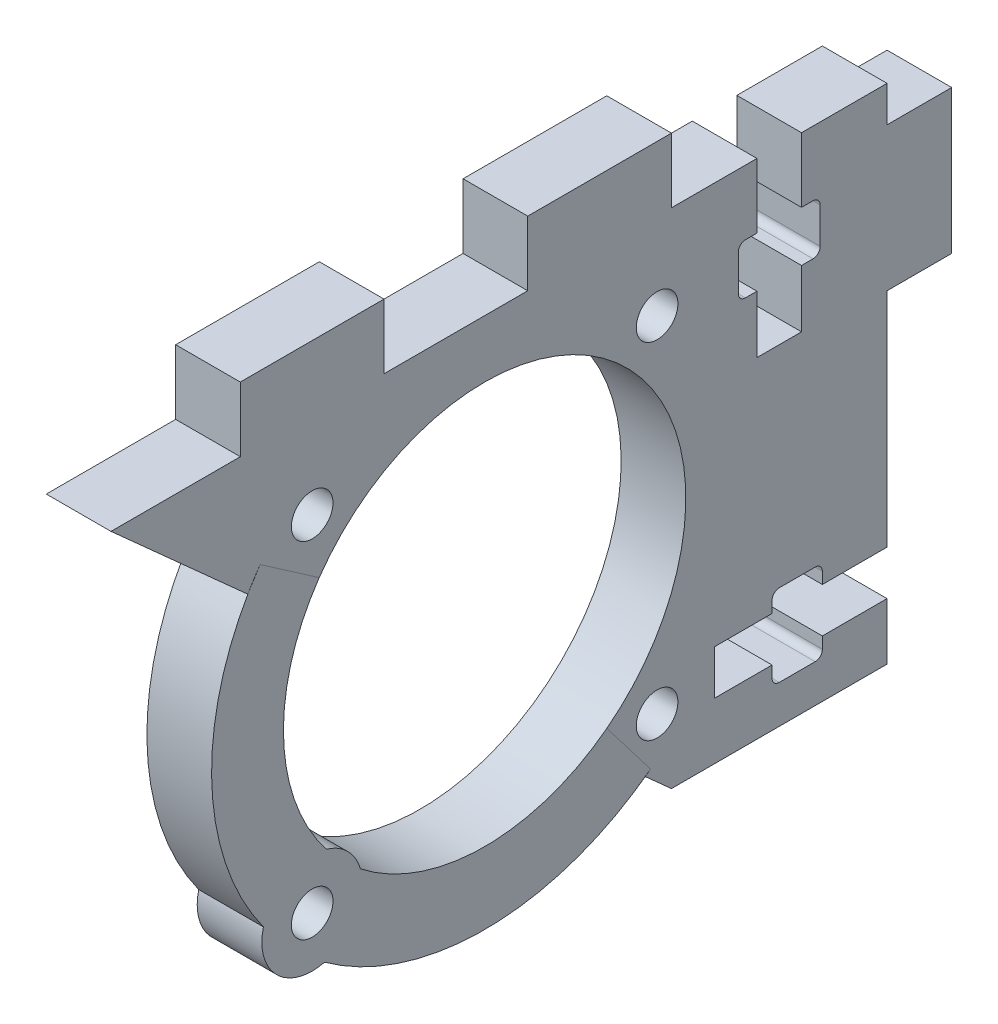
SolidWorks part; units mm, degrees
ref_plane "Front Plane" through (0, 0, 0) normal (0, 0, 1) x (1, 0, 0)
ref_plane "Top Plane" through (0, 0, 0) normal (0, 1, 0) x (1, 0, 0)
ref_plane "Right Plane" through (0, 0, 0) normal (1, 0, 0) x (0, 0, -1)
sketch "Sketch1" plane through (0, 0, 0) normal (1, 0, 0) x (0, 0, -1)
  line L0 (0, 0) -> (0, -35)
  line L1 (0, -35) -> (-54, 0)
  line L2 (-54, 0) -> (0, 0)
  dimension "D1" = 35
  dimension "D2" = 54
extrude "Boss-Extrude1" add sketch "Sketch1" along normal blind 4.5
sketch "Sketch2" plane through (4.5, 0, 0) normal (1, 0, 0) x (0, 0, -1)
  line L0 (0, -35) -> (0, 0) construction
  line L1 (-4.5, -2.5) -> (4.5, -2.5)
  line L2 (-4.5, -2.5) -> (-4.5, -12.5)
  line L3 (-4.5, -12.5) -> (4.5, -12.5)
  line L4 (4.5, -2.5) -> (4.5, -12.5)
  line L5 (-4.5, -2.5) -> (4.5, -12.5) construction
  line L6 (-4.5, -12.5) -> (4.5, -2.5) construction
  line L7 (0, 0) -> (-54, 0) construction
  point P0 (0, -7.5)
  dimension "D1" = 10
  dimension "D2" = 7.5
  dimension "D3" = 4.5
extrude "Boss-Extrude2" add sketch "Sketch2" against normal through all
sketch "Sketch3" plane through (4.5, 0, 0) normal (1, 0, 0) x (0, 0, -1)
  line L0 (0, -35) -> (-15, -35)
  line L1 (0, -25) -> (-54, 0)
  line L4 (0, -35) -> (0, -12.5) construction
  line L5 (0, -25) -> (0, -35)
  line L6 (-54, 0) -> (-15, -35)
  dimension "D1" = 15
  dimension "D2" = 10
extrude "Boss-Extrude3" add sketch "Sketch3" against normal through all
sketch "Sketch4" plane through (4.5, 0, 0) normal (1, 0, 0) x (0, 0, -1)
  line L0 (0, -29.5) -> (-12, -29.5) construction
  line L1 (0, -35) -> (0, -12.5) construction
  line L2 (0, -27.95) -> (-12, -27.95) construction
  line L3 (-12, -27.95) -> (-12, -31.05) construction
  line L4 (0, -31.05) -> (0, -27.95)
  line L5 (0, -27.95) -> (-4.5, -27.95)
  line L6 (-4.5, -27.95) -> (-4.5, -27.15)
  line L7 (-5, -26.65) -> (-7.5, -26.65)
  line L8 (-8, -27.15) -> (-8, -27.95)
  line L9 (-8, -27.95) -> (-12, -27.95)
  line L10 (-12, -27.95) -> (-12, -31.05)
  line L12 (0, -31.05) -> (-12, -31.05) construction
  line L13 (-8, -31.05) -> (-12, -31.05)
  line L14 (-8, -31.85) -> (-8, -31.05)
  line L15 (-5, -32.35) -> (-7.5, -32.35)
  line L16 (-4.5, -31.05) -> (-4.5, -31.85)
  line L17 (0, -31.05) -> (-4.5, -31.05)
  line L18 (4.5, -12.5) -> (4.5, -2.5) construction
  line L19 (0, -18.5) -> (-33.3857, -18.5) construction
  line L20 (-54, 0) -> (-15, -35) construction
  line L37 (0, -31.05) -> (-12, -31.05) construction
  arc A0 (-8, -31.85) -> (-7.5, -32.35) centre (-7.5, -31.85) ccw
  arc A1 (-5, -32.35) -> (-4.5, -31.85) centre (-5, -31.85) ccw
  arc A2 (-4.5, -27.15) -> (-5, -26.65) centre (-5, -27.15) ccw
  arc A3 (-7.5, -26.65) -> (-8, -27.15) centre (-7.5, -27.15) ccw
  point P10 (4.5, -7.5)
  point P20 (-8, -32.35)
  point P23 (-4.5, -32.35)
  point P26 (-4.5, -26.65)
  point P29 (-8, -26.65)
  dimension "D7" = 0.5
  dimension "D1" = 12
  dimension "D2" = 1.55
  dimension "D3" = 2.85
  dimension "D4" = 3.5
  dimension "D5" = 8
  dimension "D6" = 22
extrude "Cut-Extrude1" cut sketch "Sketch4" against normal through all
sketch "Sketch5" plane through (4.5, 0, 0) normal (1, 0, 0) x (0, 0, -1)
  line L0 (0, 0) -> (-54, 0) construction
  line L1 (-25, 4.5) -> (-15, 4.5)
  line L2 (-25, 4.5) -> (-25, 0)
  line L3 (0, 0) -> (-54, 0) construction
  line L4 (-15, 4.5) -> (-15, 0)
  line L5 (-25, 4.5) -> (-20, 0) construction
  line L6 (-20, 0) -> (-15, 4.5) construction
  line L7 (-30, 0) -> (-30, 4.5) construction
  line L8 (-40, 0) -> (-45, 4.5) construction
  line L9 (-35, 4.5) -> (-40, 0) construction
  line L10 (-45, 4.5) -> (-45, 0)
  line L12 (-35, 4.5) -> (-35, 0)
  line L13 (-35, 4.5) -> (-45, 4.5)
  line L14 (-20, 0) -> (-15, 4.5) construction
  line L15 (-15, 0) -> (-25, 0)
  line L16 (-35, 0) -> (-45, 0)
  point P0 (-20, 0)
  point P14 (-40, 0)
  dimension "D3" = 4.5
  dimension "D1" = 20
  dimension "D2" = 10
  dimension "D4" = 20
  dimension "D5" = 5
extrude "Boss-Extrude4" add sketch "Sketch5" against normal through all
sketch "Sketch8" [suppressed] plane through (4.5, 0, 0) normal (1, 0, 0) x (0, 0, -1)
  line L0 (-15, -30) -> (-27, -30) construction
  line L1 (-15, -35) -> (-27, -35)
  line L2 (-15, -25) -> (-27, -25)
  line L3 (-15, -35) -> (0, -35) construction
  line L4 (-15, -25) -> (-15, -35)
  arc A1 (-27, -25) -> (-27, -35) centre (-27, -30) ccw
  dimension "D5" = 5
  dimension "D1" = 0
  dimension "D2" = 12
  dimension "D3" = 0
  dimension "D4" = 10
extrude "Boss-Extrude5" [suppressed] add sketch "Sketch8" against normal up to surface (4.5 mm away) up to face at (0, -17.3125, 11.9375)
sketch "Sketch9" [suppressed] plane through (4.5, 0, 0) normal (1, 0, 0) x (0, 0, -1)
  line L0 (-27, -30) -> (-22, -30) construction
  line L1 (-27, -27) -> (-22, -27)
  line L2 (-27, -33) -> (-22, -33)
  arc A0 (-27, -27) -> (-27, -33) centre (-27, -30) ccw
  arc A1 (-22, -33) -> (-22, -27) centre (-22, -30) ccw
  point P3 (-24.5, -30)
  dimension "D1" = 3
  dimension "D2" = 5
extrude "Cut-Extrude3" [suppressed] cut sketch "Sketch9" against normal through all
sketch "Sketch10" plane through (0, 0, 0) normal (-1, 0, 0) x (0, 0, 1)
  line L0 (15, -35) -> (54, -12)
  line L1 (54, -12) -> (54, 0)
  line L3 (54, 0) -> (15, -35)
  dimension "D1" = 12
extrude "Boss-Extrude6" [suppressed] add sketch "Sketch10" against normal through all
sketch "Sketch6" plane through (4.5, 0, 0) normal (1, 0, 0) x (0, 0, -1)
  line L0 (-30, 0) -> (-30, -11) construction
  line L1 (-25, 0) -> (-35, 0) construction
  line L2 (-28.45, -11) -> (-31.55, -11) construction
  line L3 (-31.55, -11) -> (-31.55, 0) construction
  line L4 (-28.45, 0) -> (-31.55, 0)
  line L5 (-31.55, 0) -> (-31.55, -4.5)
  line L6 (-31.55, -4.5) -> (-32.35, -4.5)
  line L7 (-32.85, -5) -> (-32.85, -7.5)
  line L8 (-32.35, -8) -> (-31.55, -8)
  line L9 (-31.55, -8) -> (-31.55, -11)
  line L10 (-31.55, -11) -> (-28.45, -11)
  line L11 (-28.45, -11) -> (-28.45, 0) construction
  line L12 (-28.45, -8) -> (-28.45, -11)
  line L13 (-27.65, -8) -> (-28.45, -8)
  line L14 (-27.15, -5) -> (-27.15, -7.5)
  line L15 (-28.45, -4.5) -> (-27.65, -4.5)
  line L16 (-28.45, 0) -> (-28.45, -4.5)
  arc A0 (-32.85, -7.5) -> (-32.35, -8) centre (-32.35, -7.5) ccw
  arc A1 (-32.35, -4.5) -> (-32.85, -5) centre (-32.35, -5) ccw
  arc A2 (-27.65, -4.5) -> (-27.15, -5) centre (-27.65, -5) cw
  arc A3 (-27.15, -7.5) -> (-27.65, -8) centre (-27.65, -7.5) cw
  point P12 (-32.85, -8)
  point P15 (-32.85, -4.5)
  point P26 (-27.15, -4.5)
  point P27 (-27.15, -8)
  dimension "D2" = 1.55
  dimension "D4" = 3.5
  dimension "D6" = 0.5
  dimension "D1" = 11
  dimension "D3" = 8
  dimension "D5" = 2.85
extrude "Cut-Extrude2" [suppressed] cut sketch "Sketch6" against normal through all
sketch "Sketch11" plane through (0, 0, 0) normal (-1, 0, 0) x (0, 0, 1)
  line L0 (7.5, 0) -> (7.5, -12) construction
  line L1 (0, 0) -> (15, 0) construction
  line L2 (5.95, -12) -> (9.05, -12)
  line L3 (9.05, -12) -> (9.05, -8)
  line L4 (9.05, -8) -> (9.85, -8)
  line L5 (10.35, -7.5) -> (10.35, -5)
  line L6 (9.85, -4.5) -> (9.05, -4.5)
  line L7 (9.05, -4.5) -> (9.05, 0)
  line L8 (9.05, 0) -> (5.95, 0)
  line L9 (9.05, -8) -> (9.05, -4.5) construction
  line L10 (0, 0) -> (15, 0) construction
  line L11 (5.95, -8) -> (5.95, -4.5) construction
  line L12 (5.95, -4.5) -> (5.95, 0)
  line L13 (5.15, -4.5) -> (5.95, -4.5)
  line L14 (4.65, -7.5) -> (4.65, -5)
  line L15 (5.95, -8) -> (5.15, -8)
  line L16 (5.95, -12) -> (5.95, -8)
  arc A0 (10.35, -5) -> (9.85, -4.5) centre (9.85, -5) ccw
  arc A1 (5.15, -4.5) -> (4.65, -5) centre (5.15, -5) ccw
  arc A2 (9.85, -8) -> (10.35, -7.5) centre (9.85, -7.5) ccw
  arc A3 (4.65, -7.5) -> (5.15, -8) centre (5.15, -7.5) ccw
  point P11 (7.5, 0)
  point P22 (10.35, -4.5)
  point P25 (4.65, -4.5)
  point P28 (10.35, -8)
  point P31 (4.65, -8)
  dimension "D7" = 0.5
  dimension "D1" = 12
  dimension "D3" = 2.85
  dimension "D8" = 0.5
  dimension "D2" = 3.5
  dimension "D4" = 8
  dimension "D5" = 1.55
  dimension "D6" = 0
extrude "Cut-Extrude4" cut sketch "Sketch11" against normal through all
sketch "Sketch12" plane through (0, 0, 0) normal (-1, 0, 0) x (0, 0, 1)
  line L0 (28, -18) -> (16, -6) construction
  line L1 (28, -18) -> (28, -4) construction
  line L2 (28, -18) -> (40, -6) construction
  line L3 (28, -18) -> (14, -18) construction
  line L4 (28, -18) -> (16, -30) construction
  line L5 (28, -18) -> (16, -6) construction
  line L6 (0, -27.95) -> (0, -12.5) construction
  line L7 (25, 0) -> (35, 0) construction
  circle A0 centre (28, -18) radius 14
  circle A1 centre (16, -6) radius 1.45
  circle A2 centre (40, -6) radius 1.45
  circle A3 centre (16, -30) radius 1.45
  dimension "D1" = 28
  dimension "D2" = 2.9
  dimension "D3" = 12
  dimension "D4" = 45
  dimension "D5" = 28
  dimension "D6" = 18
extrude "FanCutout" cut sketch "Sketch12" against normal through all
sketch "Sketch13" plane through (0, 0, 0) normal (-1, 0, 0) x (0, 0, 1)
  line L0 (39.5107, -10.0311) -> (43.6217, -7.185)
  line L1 (19.4957, -29.121) -> (16.4584, -33.0928)
  line L6 (28, -18) -> (54, 0) construction
  line L7 (28, -18) -> (15, -35) construction
  arc A0 (19.4957, -29.121) -> (39.5107, -10.0311) centre (28, -18) ccw
  arc A1 (16.4584, -33.0928) -> (43.6217, -7.185) centre (28, -18) ccw
  arc A3 (40.643, -11.9871) -> (20.6593, -29.9212) centre (28, -18) ccw construction
  dimension "D1" = 5
extrude "Boss-Extrude7" add sketch "Sketch13" against normal through all
sketch "Sketch14" plane through (0, 0, 0) normal (-1, 0, 0) x (0, 0, 1)
  line L0 (28, -4) -> (28, -32) construction
  line L1 (28, -18) -> (40, -30) construction
  circle A0 centre (28, -18) radius 14 construction
  circle A1 centre (40, -30) radius 3.5
  dimension "D2" = 7
  dimension "D1" = 45
  dimension "D3" = 12
extrude "Boss-Extrude8" add sketch "Sketch14" against normal through all
sketch "Sketch15" plane through (0, 0, 0) normal (-1, 0, 0) x (0, 0, 1)
  line L0 (42.4749, -32.4749) -> (28, -18) construction
  arc A0 (39.1388, -33.3924) -> (43.3924, -29.1388) centre (40, -30) ccw construction
  circle A1 centre (40, -30) radius 1.45
  dimension "D1" = 2.9
extrude "Cut-Extrude6" cut sketch "Sketch15" against normal through all
sketch "Sketch16" [suppressed] plane through (4.5, 0, 0) normal (1, 0, 0) x (0, 0, -1)
  line L0 (0, -34.5) -> (-39, -34.5) construction
  line L1 (0, -27.95) -> (0, -12.5) construction
  line L2 (-15, -34.5) -> (-39, -34.5) construction
  line L3 (-15, -38.5) -> (-39, -38.5)
  line L4 (-15, -30.5) -> (-39, -30.5)
  arc A0 (-15, -38.5) -> (-15, -30.5) centre (-15, -34.5) ccw
  arc A1 (-39, -30.5) -> (-39, -38.5) centre (-39, -34.5) ccw
  point P5 (-27, -34.5)
  point P12 (0, -20.225)
  dimension "D1" = 4
  dimension "D2" = 34.5
  dimension "D3" = 39
  dimension "D4" = 15
extrude "Boss-Extrude9" [suppressed] add sketch "Sketch16" against normal through all
sketch "Sketch17" [suppressed] plane through (4.5, 0, 0) normal (1, 0, 0) x (0, 0, -1)
  line L0 (-43, -34.5) -> (0, -34.5) construction
  line L1 (0, -27.75) -> (0, -12.5) construction
  line L2 (-26.5, -34.5) -> (-26.5, -20.0064) construction
  arc A0 (-42.1823, -32.0766) -> (-39, -38.5) centre (-39, -34.5) ccw construction
  circle A1 centre (-39, -34.5) radius 1.55
  circle A2 centre (-14, -34.5) radius 1.55
  dimension "D1" = 2.9
  dimension "D2" = 12.5
extrude "Cut-Extrude7" [suppressed] cut sketch "Sketch17" against normal through all
sketch "Sketch18" [suppressed] plane through (4.5, 0, 0) normal (1, 0, 0) x (0, 0, -1)
  line L0 (-15, -38.5) -> (0, -35)
  line L1 (0, -35) -> (-11.0314, -35)
  line L2 (-11.0314, -35) -> (-15, -38.5)
extrude "Boss-Extrude10" [suppressed] add sketch "Sketch18" against normal through all
sketch "Sketch20" [suppressed] plane through (4.5, 0, 0) normal (1, 0, 0) x (0, 0, -1)
  line L0 (0, -35) -> (0, -31.05) construction
  line L1 (-9, -38) -> (-37.9081, -38)
  line L2 (-40.7232, -36.0371) -> (-54, 0)
  line L3 (-54, 0) -> (-15, -35)
  line L4 (-15, -35) -> (-6, -35)
  line L5 (-9, -38) -> (-6, -35)
  line L6 (-40.7232, -36.0371) -> (-40, -38) construction
  line L7 (-40, -38) -> (-37.9081, -38) construction
  arc A1 (-37.9081, -38) -> (-40.7232, -36.0371) centre (-37.9081, -35) cw
  point P0 (0, -33.025)
  point P14 (-40, -38)
  dimension "D3" = 6
  dimension "D4" = 3
  dimension "D1" = 40
  dimension "D2" = 3
  dimension "D5" = 135
extrude "Boss-Extrude11" [suppressed] add sketch "Sketch20" against normal through all
sketch "Sketch21" [suppressed] plane through (4.5, 0, 0) normal (1, 0, 0) x (0, 0, -1)
  line L0 (0, -34.5) -> (-41.2895, -34.5) construction
  line L1 (0, -35) -> (0, -31.05) construction
  line L2 (-54, 0) -> (-40.7232, -36.0371) construction
  line L3 (0, -27.95) -> (0, -12.5) construction
  circle A0 centre (-36, -34.5) radius 1.45
  circle A1 centre (-11, -34.5) radius 1.45
  dimension "D2" = 2.9
  dimension "D3" = 2.9
  dimension "D1" = 25
  dimension "D4" = 34.5
  dimension "D5" = 11
extrude "Cut-Extrude8" [suppressed] cut sketch "Sketch21" against normal through all
sketch "Sketch22" [suppressed] plane through (4.5, 0, 0) normal (1, 0, 0) x (0, 0, -1)
  line L0 (0, -27.95) -> (0, -12.5) construction
  line L1 (-25, 0) -> (-35, 0) construction
  circle A0 centre (-28, -18) radius 13.25
  dimension "D2" = 18
  dimension "D3" = 26.5
  dimension "D1" = 28
extrude "Cut-Extrude9" [suppressed] cut sketch "Sketch22" against normal through all
equation "\"X-ROD-SPACING\"=45"
equation "\"Y-ROD-SPACING\"=75"
equation "\"Z-ROD-SPACING\"=17.5"
equation "\"Y-BED-OFFSET\"=2"
equation "\"Y-BED-ROD-INSET\"=3.5"
equation "\"Y-BED-SCREW-SPACING\"=209"
equation "\"Y-BED-SCREW-CUTOUT-SLOT-HEIGHT\"=2"
equation "\"T-SLOT-NUT-FILLET-RADIUS\"=0.5"
equation "\"T-SLOT-SCREW-SHAFT-RADIUS\"=1.55"
equation "\"T-SLOT-SCREW-SHAFT-CUTOUT-LENGTH\"=11.0"
equation "\"T-SLOT-NUT-DEPTH\"=3.5"
equation "\"T-SLOT-NUT-WIDTH\"=2.85"
equation "\"T-SLOT-NUT-END-DISTANCE\"=8"
equation "\"ACRYLIC-THICKNESS\"=10"
equation "\"ACRYLIC-THICKNESS2\"=4.5"
equation "\"ACRYLIC-TAB-CUTOUT-SIZE\"=\"ACRYLIC-THICKNESS\"+\"ACRYLIC-TAB-TOLERANCE\"*2"
equation "\"ACRYLIC-TAB-WIDTH\"=\"ACRYLIC-THICKNESS\""
equation "\"ACRYLIC-M3-HOLE\"=2.9"
equation "\"SMOOTHROD-CAP-SCREW-DISTANCE\"=20"
equation "\"FRAME-WIDTH-INNER\"=370"
equation "\"NEMA17-HOLE-SPACING\"=31"
equation "\"NEMA17-CENTRAL-CUTOUT\"=22.5"
equation "\"Z-BRACKET-REACH\"=55"
equation "\"Z-ROD-INSET\"=16"
equation "\"TOP-BRACKET-SPACING\"=40"
equation "\"SMOOTHROD-X-LENGTH\"=350"
equation "\"SMOOTHROD-Y-LENGTH\"=350"
equation "\"SMOOTHROD-Z-LENGTH\"=350"
equation "\"SMOOTHROD-TIGHTENING-HEADROOM\"=.25"
equation "\"LEADSCREW-Z-LENGTH\"=300"
equation "\"SCREW-LENGTH-FRAME\"=\"ACRYLIC-THICKNESS\" + 10"
equation "\"SCREW-LENGTH-MOTOR\"=\"ACRYLIC-THICKNESS\" + 5"
equation "\"SCREW-LENGTH-EXTRUDER\"=28"
equation "\"SCREW-HEAD-RADIUS\"=6"
equation "\"PRINTED-X-SMOOTHROD-DIAMETER\"=9.0"
equation "\"PRINTED-X-SMOOTHROD-CUTOUT\"=10"
equation "\"PRINTED-X-BASE-HEIGHT\"=10"
equation "\"PRINTED-LM8UU-CUTOUT-SIZE\"=15.5"
equation "\"PRINTED-LM8UU-CUTOUT-LENGTH\"=24.5"
equation "\"PRINTED-X-IDLER-HEIGHT\"=16"
equation "\"PSU-MOUNTING-WIDTH\"=95"
equation "\"PSU-MOUNTING-HEIGHT\"=177"
equation "\"Y-BELT-TO-ROD-DISTANCE\"=20"
equation "\"SPOOL-HOLDER-ROD-SPACING\"=150"
equation "\"ACRYLIC-X-CARRIAGE-WIDTH\"=55"
equation "\"ACRYLIC-X-CARRIAGE-HEIGHT\"=75"
equation "\"ACRYLIC-X-CARRIAGE-SCREW-SPACING-X\"=15"
equation "\"ACRYLIC-X-CARRIAGE-SCREW-SPACING-Y\"=33"
equation "\"ACRYLIC-X-CARRIAGE-CENTER-TAB-SPACING\"=14"
equation "\"ACRYLIC-X-CARRIAGE-EXTRUDER-SHELF-DEPTH\"=\"ACRYLIC-X-CARRIAGE-EXTRUDER-OFFSET\" + 28"
equation "\"D2@Sketch1\"=\"ACRYLIC-X-CARRIAGE-EXTRUDER-SHELF-DEPTH\""
equation "\"D1@Boss-Extrude1\"=\"ACRYLIC-THICKNESS2\""
equation "\"D1@Sketch2\"=\"ACRYLIC-TAB-WIDTH\""
equation "\"D3@Sketch2\"=\"ACRYLIC-THICKNESS2\""
equation "\"ACRYLIC-X-CARRIAGE-LM8UU-CUTOUT-WIDTH\"=24.25"
equation "\"ACRYLIC-X-CARRIAGE-EXTRUDER-BRACE-SPACING\"=23"
equation "\"ACRYLIC-X-CARRIAGE-EXTRUDER-BRACE-HEIGHT\"=35"
equation "\"D1@Sketch1\"=\"ACRYLIC-X-CARRIAGE-EXTRUDER-BRACE-HEIGHT\""
equation "\"D1@Sketch4\"=\"T-SLOT-SCREW-SHAFT-CUTOUT-LENGTH\"+1"
equation "\"D2@Sketch4\"=\"T-SLOT-SCREW-SHAFT-RADIUS\""
equation "\"D3@Sketch4\"=\"T-SLOT-NUT-WIDTH\""
equation "\"D4@Sketch4\"=\"T-SLOT-NUT-DEPTH\""
equation "\"D5@Sketch4\"=\"T-SLOT-NUT-END-DISTANCE\""
equation "\"D7@Sketch4\"=\"T-SLOT-NUT-FILLET-RADIUS\""
equation "\"ACRYLIC-X-CARRIAGE-EXTRUDER-BRACE-SCREW-SPACING\"=22"
equation "\"D6@Sketch4\"=\"ACRYLIC-X-CARRIAGE-EXTRUDER-BRACE-SCREW-SPACING\""
equation "\"ACRYLIC-X-CARRIAGE-EXTRUDER-BRACE-TAB-OFFSET\"=20"
equation "\"D1@Sketch5\"=\"ACRYLIC-X-CARRIAGE-EXTRUDER-BRACE-TAB-OFFSET\""
equation "\"D2@Sketch5\"=\"ACRYLIC-TAB-WIDTH\""
equation "\"D3@Sketch5\"=\"ACRYLIC-THICKNESS2\""
equation "\"ACRYLIC-X-CARRIAGE-EXTRUDER-OFFSET\"=26"
equation "\"ACRYLIC-X-CARRIAGE-EXTRUDER-ANGLE\"=90"
equation "\"D1@Sketch6\"=\"T-SLOT-SCREW-SHAFT-CUTOUT-LENGTH\""
equation "\"D2@Sketch6\"=\"T-SLOT-SCREW-SHAFT-RADIUS\""
equation "\"D3@Sketch6\"=\"T-SLOT-NUT-END-DISTANCE\""
equation "\"D4@Sketch6\"=\"T-SLOT-NUT-DEPTH\""
equation "\"D5@Sketch6\"=\"T-SLOT-NUT-WIDTH\""
equation "\"D6@Sketch6\"=\"T-SLOT-NUT-FILLET-RADIUS\""
equation "\"D1@Sketch11\"=\"T-SLOT-SCREW-SHAFT-CUTOUT-LENGTH\"+1"
equation "\"D2@Sketch11\"=\"T-SLOT-NUT-DEPTH\""
equation "\"D3@Sketch11\"=\"T-SLOT-NUT-WIDTH\""
equation "\"D4@Sketch11\"=\"T-SLOT-NUT-END-DISTANCE\""
equation "\"D5@Sketch11\"=\"T-SLOT-SCREW-SHAFT-RADIUS\""
equation "\"D7@Sketch11\"=\"T-SLOT-NUT-FILLET-RADIUS\""
equation "\"D8@Sketch11\"=\"T-SLOT-NUT-FILLET-RADIUS\""
equation "\"D2@Sketch12\"=\"ACRYLIC-M3-HOLE\""
equation "\"D1@Sketch15\"=\"ACRYLIC-M3-HOLE\""
equation "\"D1@Sketch17\"=\"ACRYLIC-M3-HOLE\""
equation "\"D2@Sketch21\"=\"ACRYLIC-M3-HOLE\""
equation "\"D3@Sketch21\"=\"ACRYLIC-M3-HOLE\""
